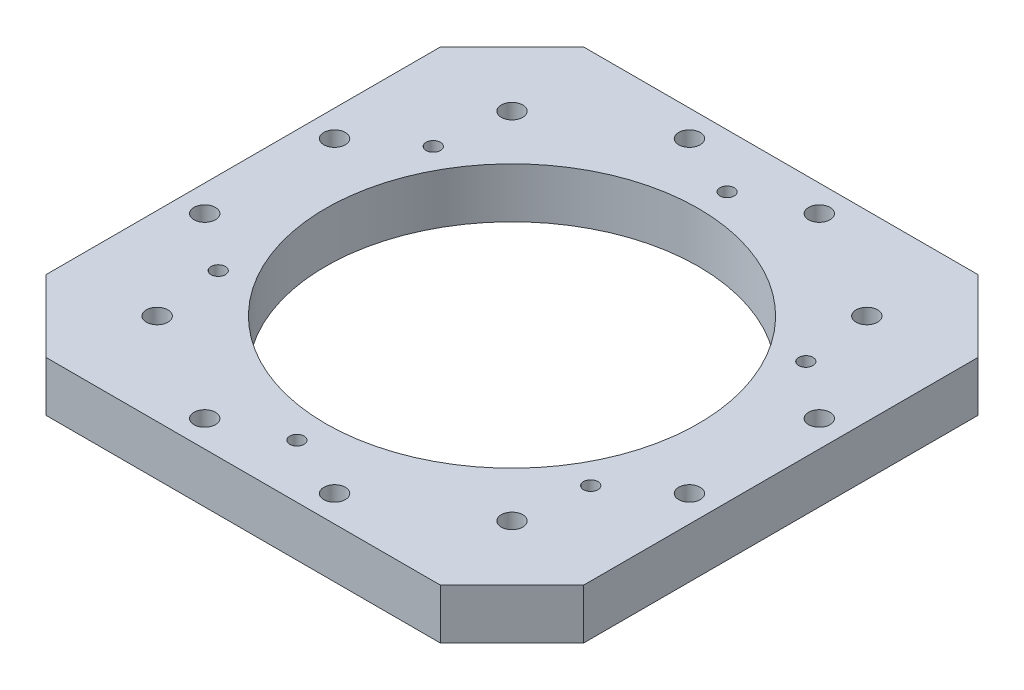
SolidWorks part; units mm, degrees
ref_plane "Front Plane" through (0, 0, 0) normal (0, 0, 1) x (1, 0, 0)
ref_plane "Top Plane" through (0, 0, 0) normal (0, 1, 0) x (1, 0, 0)
ref_plane "Right Plane" through (0, 0, 0) normal (1, 0, 0) x (0, 0, -1)
sketch "Sketch1" plane through (0, 0, 0) normal (0, 1, 0) x (1, 0, 0)
  line L0 (-53.2191, 0) -> (0, 0) construction
  line L1 (0, 0) -> (-55.1529, -14.7782) construction
  line L2 (-37.5, 37.5) -> (37.5, 37.5)
  line L3 (-37.5, 37.5) -> (-37.5, -37.5)
  line L4 (37.5, 37.5) -> (37.5, -37.5)
  line L5 (-37.5, -37.5) -> (37.5, -37.5)
  circle A0 centre (0, 0) radius 37.5 construction
  circle A1 centre (0, 0) radius 30 construction
  circle A2 centre (0, 0) radius 26
  circle A3 centre (0, 30) radius 1
  circle A4 centre (25.9808, 15) radius 1
  circle A5 centre (25.9808, -15) radius 1
  circle A6 centre (0, -30) radius 1
  circle A7 centre (-25.9808, -15) radius 1
  circle A8 centre (-25.9808, 15) radius 1
  circle A9 centre (0, 0) radius 35 construction
  circle A10 centre (-33.8074, -9.0587) radius 1.5
  circle A11 centre (-33.8074, 9.0587) radius 1.5
  circle A12 centre (-24.7487, 24.7487) radius 1.5
  circle A13 centre (-9.0587, 33.8074) radius 1.5
  circle A14 centre (9.0587, 33.8074) radius 1.5
  circle A15 centre (24.7487, 24.7487) radius 1.5
  circle A16 centre (33.8074, 9.0587) radius 1.5
  circle A17 centre (33.8074, -9.0587) radius 1.5
  circle A18 centre (24.7487, -24.7487) radius 1.5
  circle A19 centre (9.0587, -33.8074) radius 1.5
  circle A20 centre (-9.0587, -33.8074) radius 1.5
  circle A21 centre (-24.7487, -24.7487) radius 1.5
  point P19 (0, 0)
  point P47 (0, 0)
  dimension "D1" = 75
  dimension "D2" = 52
  dimension "D3" = 60
  dimension "D4" = 2
  dimension "D7" = 70
  dimension "D8" = 3
  dimension "D6" = 15
  dimension "D5" = 6
  dimension "D9" = 12
extrude "Boss-Extrude1" add sketch "Sketch1" along normal blind 7
chamfer "Chamfer1" distance 10 angle 45 4 edges at (-37.5, 3.5, 37.5) (37.5, 3.5, 37.5) (37.5, 3.5, -37.5) (-37.5, 3.5, -37.5)
